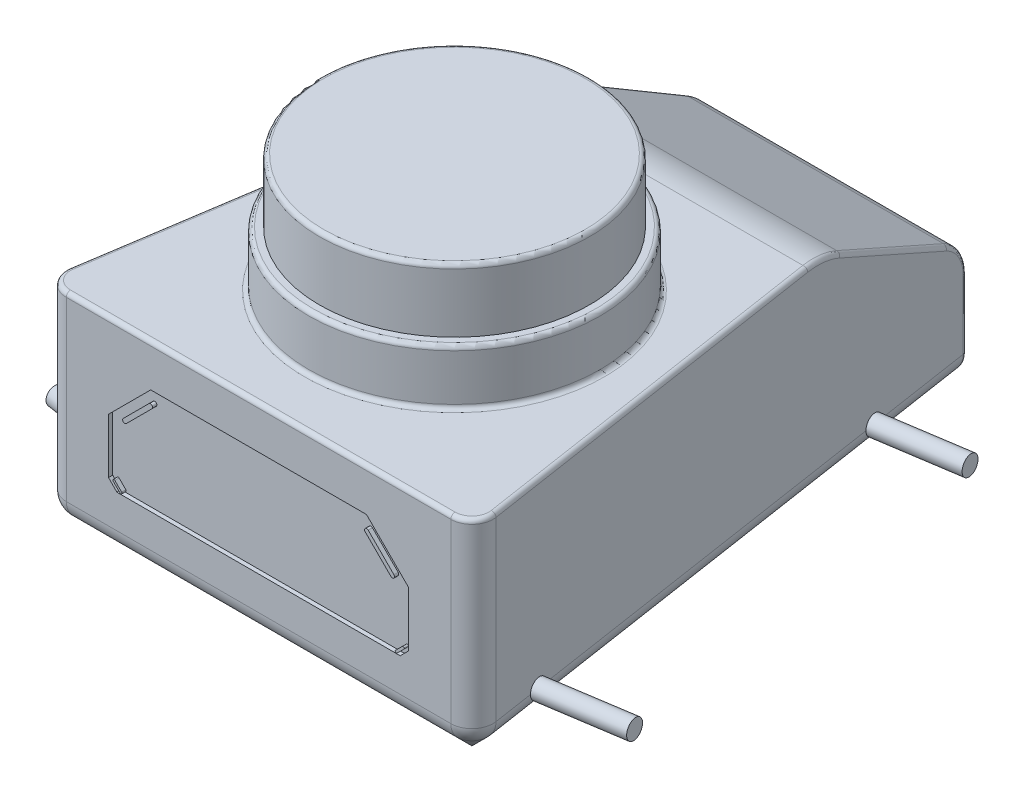
SolidWorks part; units mm, degrees
ref_plane "Front Plane" through (0, 0, 0) normal (0, 0, 1) x (1, 0, 0)
ref_plane "Top Plane" through (0, 0, 0) normal (0, 1, 0) x (1, 0, 0)
ref_plane "Right Plane" through (0, 0, 0) normal (1, 0, 0) x (0, 0, -1)
sketch "Sketch1" plane through (0, 0, 0) normal (0, 1, 0) x (1, 0, 0)
  line L0 (-51.3981, 0) -> (51.3981, 0)
  line L1 (-51.3981, 0) -> (-30.3414, 137.3808)
  line L2 (-30.3414, 137.3808) -> (30.3414, 137.3808)
  line L4 (51.3981, 0) -> (30.3414, 137.3808)
  point P4 (0, 0)
  point P10 (0, 0)
extrude "Boss-Extrude1" add sketch "Sketch1" along normal blind 50
ref_plane "Plane1" through (0, 0, 0) normal (1, 0, 0) x (0, 0, -1)
sketch "Sketch6" plane through (0, 0, 0) normal (1, 0, 0) x (0, 0, -1)
  line L0 (92.4697, 52.8242) -> (139.2927, 28.0643)
  line L1 (139.2927, 28.0643) -> (139.2927, 52.8242)
  line L2 (139.2927, 52.8242) -> (92.4697, 52.8242)
extrude "Cut-Extrude5" cut sketch "Sketch6" against normal mid plane 111
fillet "Fillet2" radius 20 1 edges at (0, 50, -97.8104)
fillet "Fillet3" radius 10 1 edges at (0, 29.0753, -137.3808)
fillet "Fillet4" radius 5 2 edges at (-51.3981, 25, 0) (51.3981, 25, 0)
chamfer "Chamfer2" distance 5 angle 45 5 edges at (-40.4285, 0, -71.5692) (40.4285, 0, -71.5692) (-49.3673, 0, -1.7433) (49.3673, 0, -1.7433) (0, 0, 0)
sketch "Sketch7" plane through (0, 0, 0) normal (0, 0, 1) x (1, 0, 0)
  line L0 (-35.5733, 17) -> (-33.5733, 15)
  line L1 (33.5733, 15) -> (35.5733, 17)
  line L2 (-25.6199, 36.6417) -> (-31.7193, 30.5423) construction
  line L3 (-25.2664, 36.2881) -> (-31.3658, 30.1887)
  line L4 (-25.5733, 40) -> (-35.5733, 30)
  line L5 (35.5733, 30) -> (25.5733, 40)
  line L6 (-25.9735, 36.9953) -> (-32.0729, 30.8958)
  line L7 (-34.2681, 17) -> (-32.649, 15.381) construction
  line L8 (-35.5733, 40) -> (-35.5733, 15)
  line L9 (-35.5733, 15) -> (35.5733, 15)
  line L10 (35.5733, 15) -> (35.5733, 40)
  line L11 (35.5733, 40) -> (-35.5733, 40)
  line L12 (-35.5733, 30) -> (-35.5733, 17)
  line L13 (-33.5733, 15) -> (33.5733, 15)
  line L14 (35.5733, 17) -> (35.5733, 30)
  line L15 (25.5733, 40) -> (-25.5733, 40)
  line L16 (-34.0785, 17.1895) -> (-32.4595, 15.5705)
  line L17 (-34.4576, 16.8105) -> (-32.8386, 15.1914)
  line L18 (0, 15) -> (0, 34.5988) construction
  line L19 (25.6199, 36.6417) -> (31.7193, 30.5423) construction
  line L20 (25.2664, 36.2881) -> (31.3658, 30.1887)
  line L21 (25.9735, 36.9953) -> (32.0729, 30.8958)
  line L22 (34.2681, 17) -> (32.649, 15.381) construction
  line L23 (34.0785, 17.1895) -> (32.4595, 15.5705)
  line L24 (34.4576, 16.8105) -> (32.8386, 15.1914)
  arc A0 (-25.2664, 36.2881) -> (-25.9735, 36.9953) centre (-25.6199, 36.6417) ccw
  arc A1 (-32.0729, 30.8958) -> (-31.3658, 30.1887) centre (-31.7193, 30.5423) ccw
  arc A2 (-34.0785, 17.1895) -> (-34.4576, 16.8105) centre (-34.2681, 17) ccw
  arc A3 (-32.8386, 15.1914) -> (-32.4595, 15.5705) centre (-32.649, 15.381) ccw
  arc A4 (25.2664, 36.2881) -> (25.9735, 36.9953) centre (25.6199, 36.6417) cw
  arc A5 (32.0729, 30.8958) -> (31.3658, 30.1887) centre (31.7193, 30.5423) cw
  arc A6 (34.0785, 17.1895) -> (34.4576, 16.8105) centre (34.2681, 17) cw
  arc A7 (32.8386, 15.1914) -> (32.4595, 15.5705) centre (32.649, 15.381) cw
  point P14 (-28.6696, 33.592)
  point P19 (-33.4585, 16.1905)
  point P32 (28.6696, 33.592)
  point P39 (33.4585, 16.1905)
  dimension "D2" = 1
  dimension "D1" = 10
extrude "Cut-Extrude6" cut sketch "Sketch7" against normal blind 1
fillet "Fillet5" radius 5 5 edges at (-40.4285, 5, -71.5692) (-49.3673, 5, -1.7433) (40.4285, 5, -71.5692) (49.3673, 5, -1.7433) (0, 5, 0)
fillet "Fillet6" radius 1 17 edges at (-27.0714, 1.7678, -137.3808) (-29.9563, 5.1577, -137.3808) (-30.3414, 15.0612, -137.3808) (-30.5612, 28.2114, -135.9467) (-33.4458, 39.7858, -117.1264) (-36.4288, 49.4114, -97.6644) (-43.8413, 50, -49.3028) (-49.3673, 50, -1.7433) (0, 50, 0) (49.3673, 50, -1.7433) (27.0714, 1.7678, -137.3808) (29.9563, 5.1577, -137.3808) (30.3414, 15.0612, -137.3808) (30.5612, 28.2114, -135.9467) (33.4458, 39.7858, -117.1264) (36.4288, 49.4114, -97.6644) (43.8413, 50, -49.3028)
sketch "Sketch8" plane through (0, 50, 0) normal (0, 1, 0) x (1, 0, 0)
  line L0 (0, 0) -> (0, 92.848) construction
  line L1 (36.1553, 92.848) -> (-36.1553, 92.848) construction
  circle A0 centre (0, 46.424) radius 34.5275
extrude "Boss-Extrude2" add sketch "Sketch8" along normal blind 13
fillet "Fillet7" radius 1 1 edges at (0, 63, -11.8965)
fillet "Fillet8" radius 1 1 edges at (0, 50, -80.9515)
sketch "Sketch9" plane through (0, 63, 0) normal (0, 1, 0) x (1, 0, 0)
  circle A0 centre (0, 46.424) radius 32
  dimension "D1" = 64
extrude "Boss-Extrude3" add sketch "Sketch9" along normal blind 15
fillet "Fillet9" radius 1 1 edges at (0, 78, -14.424)
sketch "Sketch10" plane through (50.2183, 0, -7.6971) normal (0.9885, 0, -0.1515) x (-0.1515, 0, -0.9885)
  line L0 (-1.9622, 7.0711) -> (130.3398, 7.0711) construction
  circle A0 centre (105.0378, 7.0711) radius 2.25
  circle A1 centre (10.0378, 7.0711) radius 2.25
  dimension "D4" = 4.5
  dimension "D1" = 95
  dimension "D2" = 12
  dimension "D3" = 25.302
extrude "Boss-Extrude4" add sketch "Sketch10" along normal blind 20
sketch "Sketch11" plane through (-50.2183, 0, -7.6971) normal (-0.9885, 0, -0.1515) x (-0.1515, 0, 0.9885)
  line L0 (-130.3398, 7.0711) -> (1.9622, 7.0711) construction
  circle A0 centre (-105.0378, 7.0711) radius 2.25
  circle A1 centre (-10.0378, 7.0711) radius 2.2546
  dimension "D4" = 4.5
  dimension "D1" = 95
  dimension "D2" = 12
  dimension "D3" = 25.302
extrude "Boss-Extrude5" add sketch "Sketch11" along normal blind 20
scale "Scale1" scale about centroid uniform scaling yes scale factor 1
